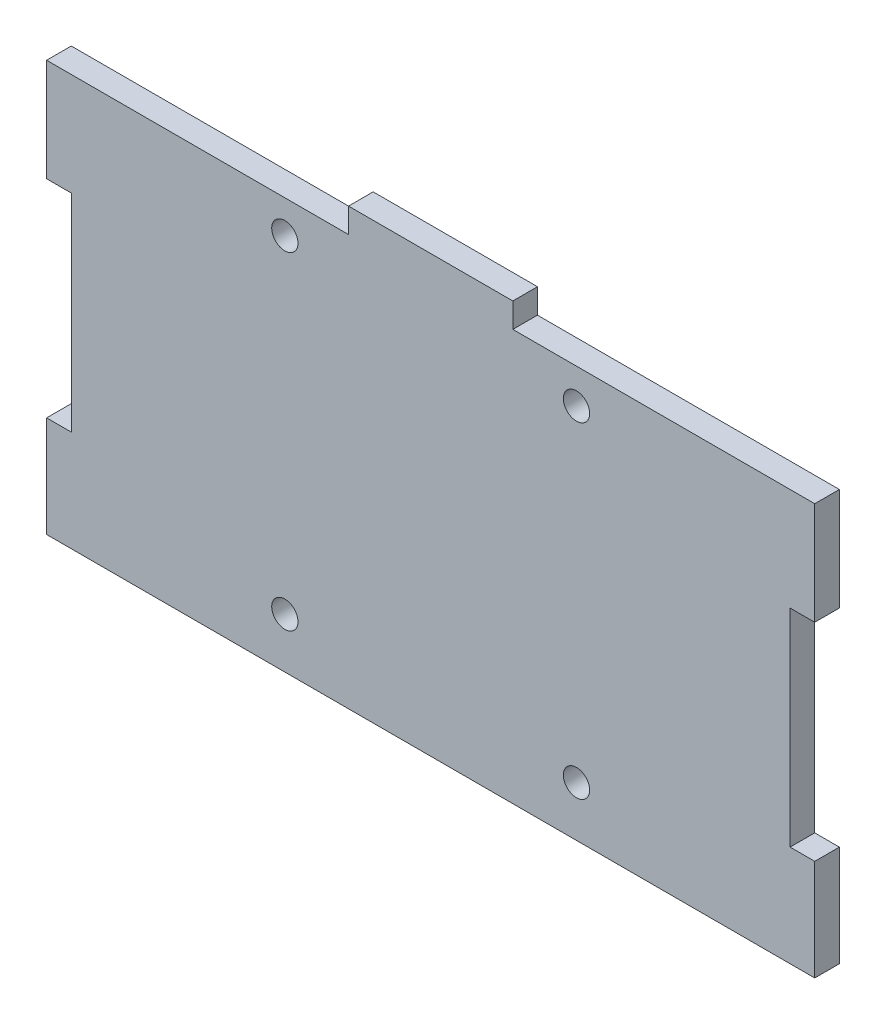
SolidWorks part; units mm, degrees
ref_plane "Plan de face" through (0, 0, 0) normal (0, 0, 1) x (1, 0, 0)
ref_plane "Plan de dessus" through (0, 0, 0) normal (0, 1, 0) x (1, 0, 0)
ref_plane "Plan de droite" through (0, 0, 0) normal (1, 0, 0) x (0, 0, -1)
sketch "Esquisse1" plane through (0, 0, 0) normal (0, 0, 1) x (1, 0, 0)
  line L1 (46.75, -25) -> (-46.75, -25)
  line L2 (46.75, -25) -> (46.75, -12.7)
  line L3 (46.75, 25) -> (26.2, 25)
  line L4 (-46.75, -25) -> (-46.75, -12.7)
  line L5 (46.75, -25) -> (-46.75, 25) construction
  line L6 (46.75, 25) -> (-46.75, -25) construction
  line L18 (0, 42.5868) -> (0, -42.8016) construction
  line L31 (-26.2, 25) -> (-46.75, 25)
  line L32 (23, 25) -> (-23, 25)
  line L33 (-46.75, -12.7) -> (-43.75, -12.7)
  line L34 (46.75, 12.5) -> (43.75, 12.5)
  line L36 (46.75, -12.7) -> (43.75, -12.7)
  line L37 (43.75, 12.5) -> (43.75, -12.7)
  line L38 (-43.75, 12.5) -> (-43.75, -12.7)
  line L39 (-46.75, 12.5) -> (-43.75, 12.5)
  line L41 (-46.75, 12.5) -> (-46.75, 25)
  line L42 (46.75, 12.5) -> (46.75, 25)
  line L43 (-26.2, 25) -> (-23, 25)
  line L44 (23, 25) -> (26.2, 25)
  point P0 (0, 0)
  dimension "D1" = 50
  dimension "D2" = 93.5
  dimension "D15" = 25.2
  dimension "D16" = 3
extrude "Boss.-Extru.1" add sketch "Esquisse1" along normal blind 3
sketch "Esquisse2" plane through (0, 0, 3) normal (0, 0, 1) x (1, 0, 0)
  line L0 (46.75, 25) -> (-46.75, 25) construction
  line L1 (-10, 25) -> (10, 25)
  line L2 (-10, 25) -> (-10, 28)
  line L3 (-10, 28) -> (10, 28)
  line L4 (10, 25) -> (10, 28)
  point P6 (0, 28)
  dimension "D1" = 20
  dimension "D2" = 3
extrude "Boss.-Extru.2" add sketch "Esquisse2" against normal blind 3
sketch "Sketch1" plane through (0, 0, 3) normal (0, 0, 1) x (1, 0, 0)
  circle A0 centre (-17.75, 21) radius 1.6
  dimension "D1" = 3.2
extrude "Cut-Extrude1" cut sketch "Sketch1" against normal through all
sketch "Sketch2" plane through (0, 0, 0) normal (0, 0, -1) x (-1, 0, 0)
  circle A0 centre (-17.75, 20.8) radius 1.6
extrude "Cut-Extrude2" cut sketch "Sketch2" against normal through all
sketch "Sketch3" plane through (0, 0, 3) normal (0, 0, 1) x (1, 0, 0)
  circle A0 centre (17.75, -18.9) radius 1.6
  circle A1 centre (-17.75, -18.9) radius 1.6
extrude "Cut-Extrude3" cut sketch "Sketch3" against normal through all
